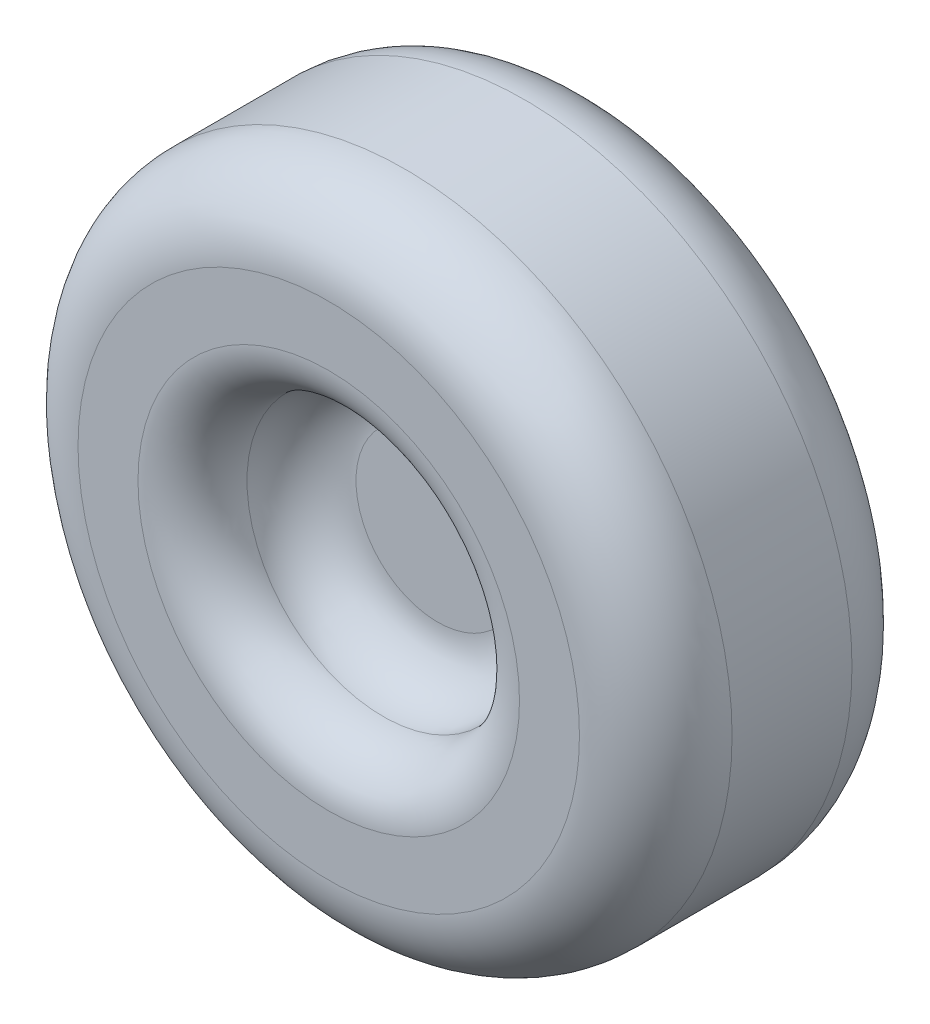
SolidWorks part; units mm, degrees
ref_plane "Front Plane" through (0, 0, 0) normal (0, 0, 1) x (1, 0, 0)
ref_plane "Top Plane" through (0, 0, 0) normal (0, 1, 0) x (1, 0, 0)
ref_plane "Right Plane" through (0, 0, 0) normal (1, 0, 0) x (0, 0, -1)
sketch "Sketch1" plane through (0, 0, 0) normal (0, 0, 1) x (1, 0, 0)
  circle A0 centre (0, 0) radius 30
  dimension "D1" = 60
extrude "Boss-Extrude1" add sketch "Sketch1" along normal blind 25
sketch "Sketch2" plane through (0, 0, 25) normal (0, 0, 1) x (1, 0, 0)
  circle A0 centre (0, 0) radius 12.5
  dimension "D1" = 25
extrude "Cut-Extrude1" cut sketch "Sketch2" against normal blind 10
fillet "Fillet1" radius 5 2 edges at (12.5, 0, 15) (12.5, 0, 25)
fillet "Fillet2" radius 7 2 edges at (30, 0, 25) (30, 0, 0)
